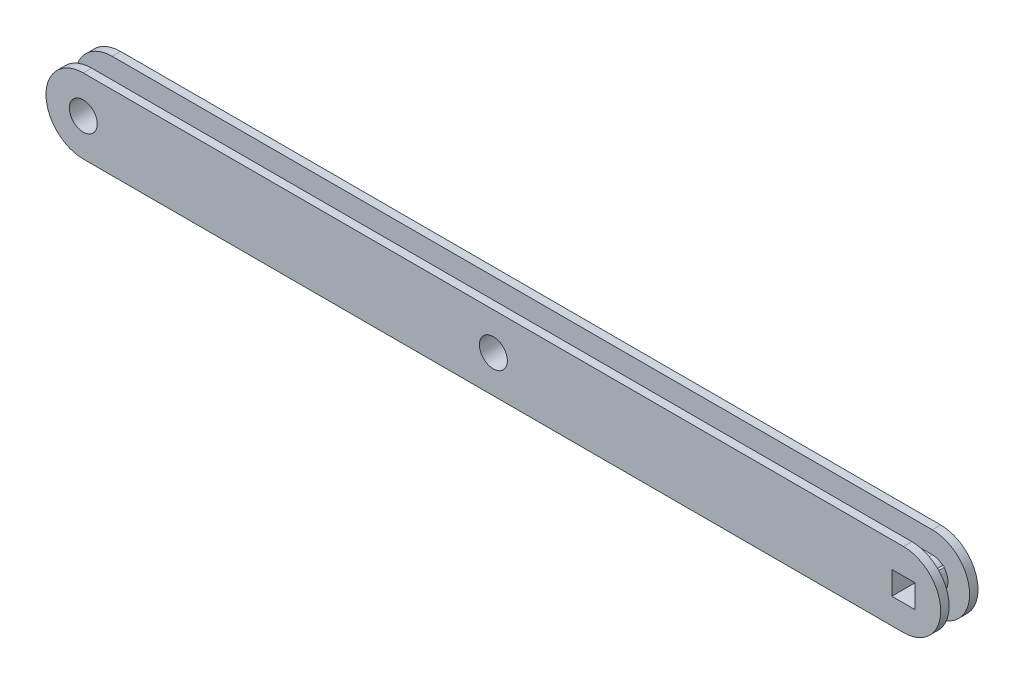
SolidWorks part; units mm, degrees
note: '?' marks a value the reader was unsure of. The reader was unsure of these and kept them because the rebuilt part matched: shared geometry of "Esquisse2<3>".
ref_plane "Plan de face" through (0, 0, 0) normal (0, 0, 1) x (1, 0, 0)
ref_plane "Plan de dessus" through (0, 0, 0) normal (0, 1, 0) x (1, 0, 0)
ref_plane "Plan de droite" through (0, 0, 0) normal (1, 0, 0) x (0, 0, -1)
sketch "Esquisse1" plane through (0, 0, 0) normal (0, 0, 1) x (1, 0, 0)
  line L4 (0, 0) -> (-152.4, 0)
  line L5 (-152.4, 0) -> (-152.4, 12.7)
  line L6 (-152.4, 12.7) -> (0, 12.7)
  line L7 (0, 12.7) -> (0, 0)
  dimension "D1" = 12.7
  dimension "D2" = 152.4
extrude "Boss.-Extru.1" add sketch "Esquisse1" against normal blind 6.35
sketch "Esquisse2" plane through (0, 0, 0) normal (0, 0, 1) x (1, 0, 0)
  line L0 (0, 12.7) -> (-152.4, 12.7) construction
  line L1 (-152.4, 0) -> (0, 0) construction
  line L2 (-152.4, 12.7) -> (-152.4, 0) construction
  line L3 (-6.35, 12.7) -> (0, 12.7)
  line L4 (0, 12.7) -> (0, 0)
  line L5 (0, 0) -> (0, 12.7) construction
  line L6 (0, 0) -> (-6.35, 0)
  line L7 (-146.05, 12.7) -> (-152.4, 12.7)
  line L8 (-152.4, 12.7) -> (-152.4, 0)
  line L9 (-152.4, 0) -> (-146.05, 0)
  line L11 (-8.7313, 3.9687) -> (-3.9688, 3.9687)
  line L12 (-8.7313, 3.9687) -> (-8.7313, 8.7312)
  line L13 (-8.7313, 8.7312) -> (-3.9688, 8.7312)
  line L14 (-3.9688, 3.9687) -> (-3.9688, 8.7312)
  line L15 (-8.7313, 3.9687) -> (-3.9688, 8.7312) construction
  line L16 (-8.7313, 8.7312) -> (-3.9688, 3.9687) construction
  line L17 (-8.0338, 4.6662) -> (-4.6662, 4.6662)
  line L18 (-8.0338, 4.6662) -> (-8.0338, 8.0338)
  line L19 (-8.0338, 8.0338) -> (-4.6662, 8.0338)
  line L20 (-4.6662, 4.6662) -> (-4.6662, 8.0338)
  line L21 (-8.0338, 4.6662) -> (-4.6662, 8.0338) construction
  line L22 (-8.0338, 8.0338) -> (-4.6662, 4.6662) construction
  line L23 (-8.3338, 4.3662) -> (-4.3662, 4.3662)
  line L24 (-8.3338, 4.3662) -> (-8.3338, 8.3338)
  line L25 (-8.3338, 8.3338) -> (-4.3662, 8.3338)
  line L26 (-7.9338, 4.7662) -> (-7.9338, 7.9338)
  line L27 (-7.9338, 7.9338) -> (-4.7662, 7.9338)
  line L28 (-4.7662, 4.7662) -> (-4.7662, 7.9338)
  line L29 (-7.9338, 4.7662) -> (-4.7662, 4.7662)
  line L30 (-4.3662, 4.3662) -> (-4.3662, 8.3338)
  line L31 (-8.3338, 4.3662) -> (-4.3662, 8.3338) construction
  line L32 (-8.3338, 8.3338) -> (-4.3662, 4.3662) construction
  circle A0 centre (-146.05, 6.35) radius 2.3813
  circle A1 centre (-6.35, 6.35) radius 2.3813
  circle A2 centre (-76.2, 6.35) radius 2.3813
  arc A3 (-146.05, 12.7) -> (-146.05, 0) centre (-146.05, 6.35) ccw
  arc A4 (-6.35, 12.7) -> (-6.35, 0) centre (-6.35, 6.35) cw
  line M1 (0, 0) -> (0, 12.7)
  line M2 (0, 12.7) -> (-152.4, 12.7)
  line M3 (-152.4, 12.7) -> (-152.4, 0)
  line M4 (-152.4, 0) -> (0, 0)
  dimension "D1" = 4.7625
  dimension "D4" = 4.7625
  dimension "D7" = 4.7625
  dimension "D2" = 6.35
  dimension "D3" = 6.35
  dimension "D5" = 6.35
  dimension "D6" = 6.35
  dimension "D8" = 69.85
  dimension "D9" = 4.7625
  dimension "D10" = 4.7625
  dimension "D12" = 0.3
  dimension "D11" = 0.1
extrude "Enlèv. mat.-Extru.1" cut sketch "Esquisse2" against normal through all contours A0 | A2 | A4 L4 M2 | A4 M1 M4 | A3 M2 M3 | A3 L8 M4 | L26 L29 L28 L27 | L17 L20 L19 L18 L29 L26 L27 L28 | L19 A1 L25 | A1 L25 L24 | L18 A1 L24 | A1 L30 L25 | L30 A1 L20 | L17 A1 L23 | A1 L24 L23 | A1 L23 L30
ref_plane "Plane1" through (0, 0, -3.175) normal (0, 0, 1) x (1, 0, 0)
ref_plane "Plane2" through (0, 6.35, 0) normal (0, 1, 0) x (1, 0, 0)
sketch "Sketch1" plane through (0, 6.35, 0) normal (0, 1, 0) x (1, 0, 0)
  line L0 (-146.05, 6.35) -> (-146.05, 0) construction
  line L1 (-6.35, 6.35) -> (-146.05, 6.35) construction
  line L2 (-6.35, 0) -> (-146.05, 0) construction
  line L3 (-146.05, 6.35) -> (-146.05, 0) construction
  line L4 (-148.4313, 6.35) -> (-148.4313, 0) construction
  line L5 (-146.05, 6.35) -> (-152.4, 6.35) construction
  line L6 (-152.4, 0) -> (-146.05, 0) construction
  line L7 (-152.4, 4.9225) -> (-150.5585, 4.9225)
  line L8 (-152.4, 6.35) -> (-152.4, 0) construction
  line L11 (-148.717, 4.9225) -> (-148.717, 1.4275)
  line L14 (-150.5585, 1.4275) -> (-152.4, 1.4275)
  line L15 (-152.4, 1.4275) -> (-152.4, 4.9225)
  line L16 (-150.5585, 4.9225) -> (-148.717, 4.9225)
  line L17 (-150.5585, 1.4275) -> (-148.717, 1.4275)
  line L18 (-152.4, 4.9225) -> (-166.5708, 4.9225)
  line L19 (-166.5708, 4.9225) -> (-166.5708, 1.4275)
  line L20 (-166.5708, 1.4275) -> (-152.4, 1.4275)
  point P18 (-148.4313, 3.175)
  point P21 (-148.717, 3.175)
  dimension "D1" = 2.3812
  dimension "D2" = 3.495
  dimension "D4" = 14.1708
  dimension "D5" = 1.8415
revolve "Cut-Revolve1" cut sketch "Sketch1" angle 180 mid plane about L0
ref_plane "Plane3" through (-76.2, 0, 0) normal (1, 0, 0) x (0, 0, -1)
mirror "Mirror1" about plane through (-76.2, 0, 0) normal (1, 0, 0) of "Cut-Revolve1"
sketch "Sketch2" plane through (0, 0, 0) normal (1, 0, 0) x (0, 0, -1)
  line L0 (1.4275, 9.017) -> (1.4275, 12.7) construction
  line L1 (1.4275, 9.017) -> (4.9225, 9.017)
  line L2 (1.4275, 9.017) -> (1.4275, 12.7)
  line L3 (1.4275, 12.7) -> (4.9225, 12.7)
  line L4 (4.9225, 9.017) -> (4.9225, 12.7)
  line L5 (4.9225, 12.7) -> (4.9225, 9.017) construction
  line L6 (4.9225, 12.7) -> (1.4275, 12.7) construction
  line L7 (4.9225, 9.017) -> (1.4275, 9.017) construction
  dimension "D1" = 3.495
extrude "Cut-Extrude1" cut sketch "Sketch2" against normal through all
mirror "Mirror2" about plane through (0, 6.35, 0) normal (0, 1, 0) of "Cut-Extrude1"
ref_plane "Plane4" through (-6.35, 0, 0) normal (-1, 0, 0) x (0, 0, 1)
ref_plane "Plane5" through (0, 6.35, 0) normal (0, -1, 0) x (-1, 0, 0)
ref_axis "Axis1" through (-6.35, 6.35, -0.3175) along (0, 0, 1)?
extrude "Cut-Extrude2" cut sketch "Esquisse2<3>" against normal through all contours L17 L20 L19 L18 L29 L26 L27 L28
sketch "Esquisse2<3>" plane through (0, 0, 0) normal (0, 0, 1) x (1, 0, 0) same geometry as "Esquisse2"
